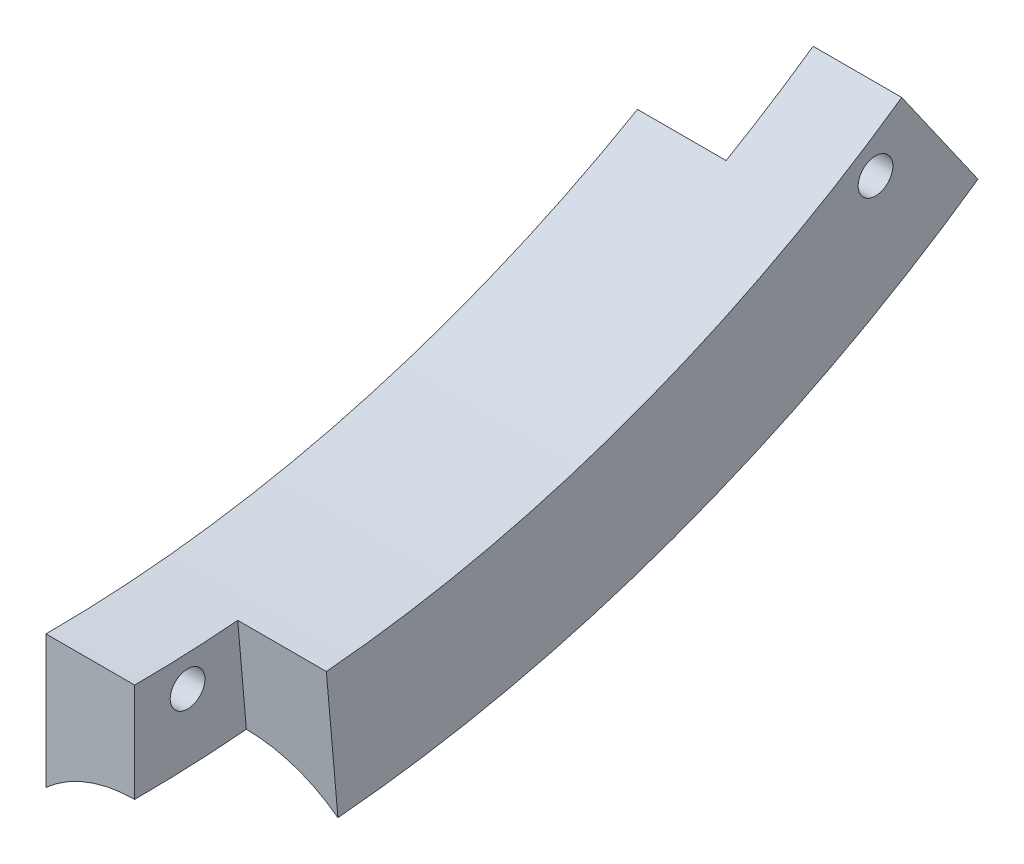
SolidWorks part; units mm, degrees
ref_plane "Front Plane" through (0, 0, 0) normal (1, 0, 0) x (0, 1, 0)
ref_plane "Top Plane" through (0, 0, 0) normal (0, 0, 1) x (0, 1, 0)
ref_plane "Right Plane" through (0, 0, 0) normal (0, 1, 0) x (-1, 0, 0)
sketch "Sketch1" plane through (0, 0, 0) normal (0, 0, 1) x (0, 1, 0)
  line L0 (0, 0) -> (0, 25.4)
  line L1 (0, 25.4) -> (-19.05, 25.4)
  line L2 (0, 0) -> (-19.05, 0)
  line L3 (169.5196, 25.4) -> (169.5196, 0) construction
  arc A0 (-19.05, 25.4) -> (-19.05, 0) centre (-33.249, 12.7) cw
  point P10 (-4.445, 0)
  dimension "D4" = 19.05
  dimension "D1" = 173.9646
  dimension "D2" = 25.4
  dimension "D3" = 19.05
  dimension "D5" = 4.445
revolve "Revolve1" add sketch "Sketch1" angle 35 about L3
sketch "Sketch2" plane through (0, 0, 0) normal (1, 0, 0) x (0, 1, 0)
  line L4 (-19.05, 0) -> (169.5196, 0)
  line L5 (169.5196, 0) -> (-18.3324, -16.4349)
  arc A4 (-19.05, 0) -> (15.0524, -108.1591) centre (169.5196, 0) ccw construction
  arc A5 (-18.3324, -16.4349) -> (-19.05, 0) centre (169.5196, 0) cw
  dimension "D1" = 5
extrude "Cut-Extrude1" cut sketch "Sketch2" against normal blind 12.7
sketch "Sketch3" plane through (-25.4, 0, 0) normal (-1, 0, 0) x (0, -1, 0)
  line L2 (-15.0524, -108.1591) -> (-169.5196, 0)
  line L3 (-169.5196, 0) -> (-6.2135, -94.2848)
  arc A4 (-15.0524, -108.1591) -> (19.05, 0) centre (-169.5196, 0) ccw construction
  arc A5 (-6.2135, -94.2848) -> (-15.0524, -108.1591) centre (-169.5196, 0) cw
  dimension "D1" = 5
extrude "Cut-Extrude2" cut sketch "Sketch3" against normal blind 12.7
sketch "Sketch4" plane through (0, 0, 0) normal (1, 0, 0) x (0, 1, 0)
  line L9 (15.0524, -108.1591) -> (30.6573, -97.2324) construction
  circle A2 centre (169.5196, 0) radius 173.9646 construction
  point P28 (-4.2794, -7.5882)
  point P30 (22.7993, -93.4711)
  point P40 (22.8548, -102.6958)
  point P44 (0, 0)
  dimension "D1" = 347.9292
  dimension "D2" = 30
  dimension "D3" = 2.5
hole_wizard "#9 (0.196) Diameter Hole1" positions "Sketch4" profile "Sketch5" hole size "#9" standard "ANSI Inch"
sketch "Sketch5" plane through (0, 22.7993, -93.4711) normal (0, 1, 0) x (0, 0, -1)
  line L0 (0, 0) -> (0, 25.4)
  line L1 (0, 25.4) -> (2.4892, 25.4)
  line L2 (2.4892, 25.4) -> (2.4892, 0)
  line L5 (2.4892, 0) -> (0, 0)
  line L11 (0, -6.35) -> (0, 107.95) construction
  dimension "Thru Hole Dia." = 4.9784
  dimension "Thru Hole Depth" = 25.4
